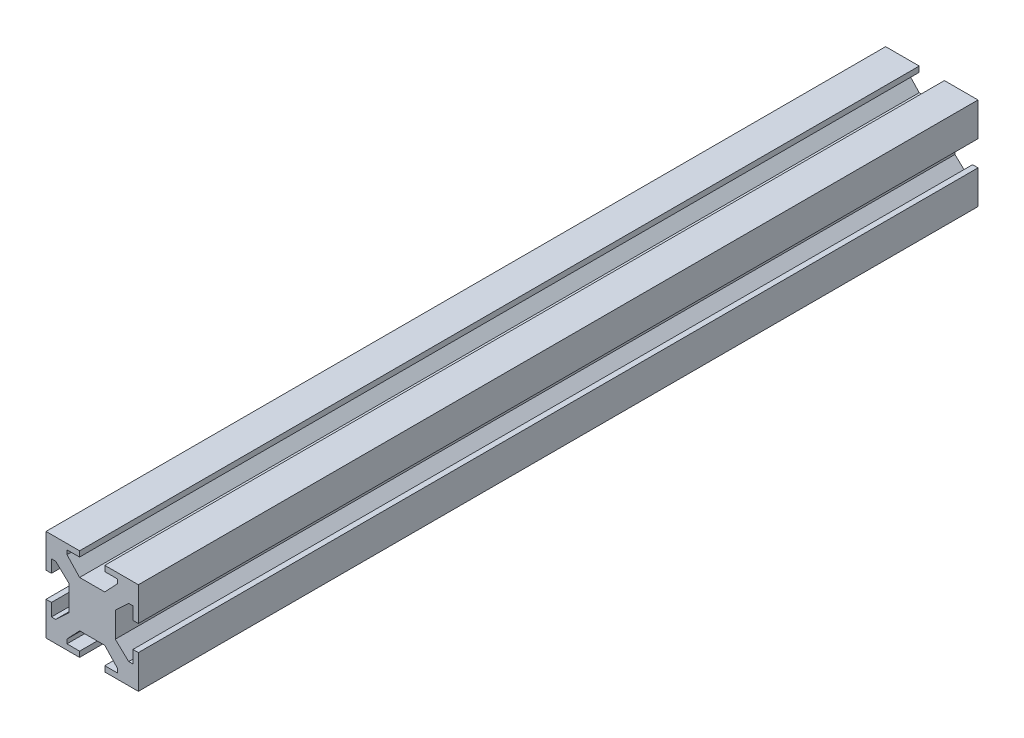
SolidWorks part; units mm, degrees
ref_plane "Front Plane" through (0, 0, 0) normal (0, 0, 1) x (1, 0, 0)
ref_plane "Top Plane" through (0, 0, 0) normal (0, 1, 0) x (1, 0, 0)
ref_plane "Right Plane" through (0, 0, 0) normal (1, 0, 0) x (0, 0, -1)
sketch "Sketch1" plane through (0, 0, 0) normal (0, 0, 1) x (1, 0, 0)
  line L1 (22, 0) -> (14, 0)
  line L2 (22, 0) -> (22, -8)
  line L3 (22, -22) -> (14, -22)
  line L4 (0, 0) -> (0, -8)
  line L6 (20.7, -14) -> (22, -14)
  line L7 (22, -11) -> (16.5, -11) construction
  line L8 (22, -14) -> (22, -22)
  line L9 (22, -8) -> (22, -11) construction
  line L10 (22, -11) -> (22, -14) construction
  line L11 (20.7, -14) -> (20.7, -17)
  line L12 (20.7, -17) -> (19.7, -17)
  line L13 (19.7, -17) -> (16.5, -14)
  line L14 (16.5, -14) -> (16.5, -8)
  line L16 (17, -19.7) -> (14, -16.5)
  line L17 (20.7, -8) -> (22, -8)
  line L18 (20.7, -8) -> (20.7, -5)
  line L19 (20.7, -5) -> (19.7, -5)
  line L20 (19.7, -5) -> (16.5, -8)
  line L21 (0, -11) -> (22, -11) construction
  line L22 (8, -16.5) -> (14, -16.5)
  line L23 (5, -19.7) -> (8, -16.5)
  line L24 (5, -20.7) -> (5, -19.7)
  line L25 (8, -20.7) -> (5, -20.7)
  line L26 (8, -20.7) -> (8, -22)
  line L27 (14, -20.7) -> (14, -22)
  line L28 (14, -20.7) -> (17, -20.7)
  line L29 (17, -20.7) -> (17, -19.7)
  line L30 (2.3, -17) -> (5.5, -14)
  line L31 (5.5, -8) -> (5.5, -14)
  line L32 (2.3, -5) -> (5.5, -8)
  line L33 (1.3, -5) -> (2.3, -5)
  line L34 (1.3, -8) -> (1.3, -5)
  line L35 (1.3, -8) -> (0, -8)
  line L36 (1.3, -14) -> (0, -14)
  line L37 (1.3, -14) -> (1.3, -17)
  line L38 (1.3, -17) -> (2.3, -17)
  line L39 (5, -2.3) -> (8, -5.5)
  line L40 (14, -5.5) -> (8, -5.5)
  line L41 (17, -2.3) -> (14, -5.5)
  line L42 (17, -1.3) -> (17, -2.3)
  line L43 (14, -1.3) -> (17, -1.3)
  line L44 (14, -1.3) -> (14, 0)
  line L45 (8, -1.3) -> (8, 0)
  line L46 (8, -1.3) -> (5, -1.3)
  line L47 (5, -1.3) -> (5, -2.3)
  line L48 (8, 0) -> (0, 0)
  line L49 (14, 0) -> (8, 0) construction
  line L50 (0, -14) -> (0, -22)
  line L51 (0, -8) -> (0, -11) construction
  line L52 (0, -11) -> (0, -14) construction
  line L53 (8, -22) -> (0, -22)
  line L54 (14, -22) -> (8, -22) construction
  point P6 (11, -11)
  point P54 (5.5, -11)
  dimension "D1" = 22
  dimension "D2" = 6
  dimension "D3" = 22
  dimension "D4" = 1.3
  dimension "D5" = 5.5
  dimension "D6" = 6
  dimension "D7" = 1
  dimension "D8" = 3
  dimension "D9" = 4
extrude "Boss-Extrude1" add sketch "Sketch1" along normal blind 200
ref_plane "Plane1" through (0, -11, 0) normal (0, -1, 0) x (-1, 0, 0)
